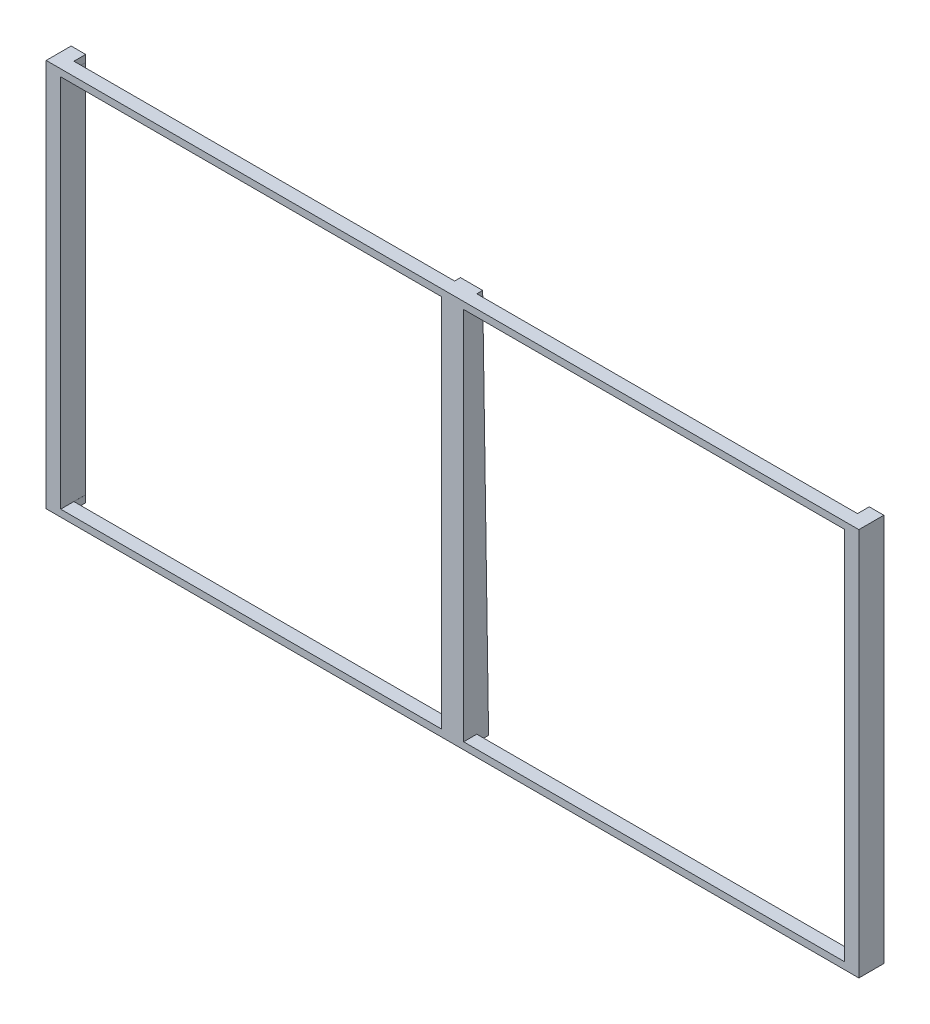
SolidWorks part; units mm, degrees
ref_plane "Спереди" through (0, 0, 0) normal (0, 0, 1) x (1, 0, 0)
ref_plane "Сверху" through (0, 0, 0) normal (0, 1, 0) x (1, 0, 0)
ref_plane "Справа" through (0, 0, 0) normal (1, 0, 0) x (0, 0, -1)
sketch "Эскиз1" plane through (0, 0, 0) normal (0, 0, 1) x (1, 0, 0)
  line L1 (-2930, 1400) -> (2930, 1400)
  line L2 (-2930, 1400) -> (-2930, -1400)
  line L3 (-2930, -1400) -> (2930, -1400)
  line L4 (2930, 1400) -> (2930, -1400)
  line L5 (-2930, 1400) -> (2930, -1400) construction
  line L6 (-2930, -1400) -> (2930, 1400) construction
  line L7 (-2825.3571, 1350) -> (-80, 1350)
  line L8 (-2825.3571, 1350) -> (-2825.3571, -1350)
  line L9 (-2825.3571, -1350) -> (-80, -1350)
  line L10 (-80, 1350) -> (-80, -1350)
  line L11 (80, 1350) -> (2825.3571, 1350)
  line L12 (80, 1350) -> (80, -1350)
  line L13 (80, -1350) -> (2825.3571, -1350)
  line L14 (2825.3571, 1350) -> (2825.3571, -1350)
  point P0 (0, 0)
extrude "Бобышка-Вытянуть1" add sketch "Эскиз1" along normal blind 180
sketch "Эскиз2" plane through (0, -1400, 0) normal (0, -1, 0) x (1, 0, 0)
  line L2 (-2825, 85) -> (-80, 85)
  line L3 (-2825, 85) -> (-2825, 0)
  line L4 (-2825, 0) -> (-80, 0)
  line L5 (-80, 85) -> (-80, 0)
  line L6 (-2825, 85) -> (-80, 0) construction
  line L7 (-2825, 0) -> (-80, 85) construction
  line L8 (0, 424.0898) -> (0, -233.7336) construction
  line L9 (2825, 0) -> (80, 85) construction
  line L10 (2825, 85) -> (80, 0) construction
  line L11 (80, 85) -> (80, 0)
  line L12 (2825, 0) -> (80, 0)
  line L13 (2825, 85) -> (2825, 0)
  line L14 (2825, 85) -> (80, 85)
  line L15 (-2930, 0) -> (2930, 0) construction
  point P2 (-1452.5, 42.5)
  point P15 (1452.5, 42.5)
extrude "Вырез-Вытянуть1" cut sketch "Эскиз2" against normal through all
sketch "Эскиз3" plane through (-80, 0, 0) normal (-1, 0, 0) x (0, 0, 1)
  line L0 (0, 1400) -> (0, -1400)
  line L1 (0, 1400) -> (85, 1400) construction
  line L2 (0, -1400) -> (0, 1400) construction
  line L3 (0, -1400) -> (42.5, 1400)
  line L4 (42.5, 1400) -> (0, 1400)
extrude "Вырез-Вытянуть2" cut sketch "Эскиз3" against normal up to surface (160 mm away) up to face at (80, 0, 87.5)
